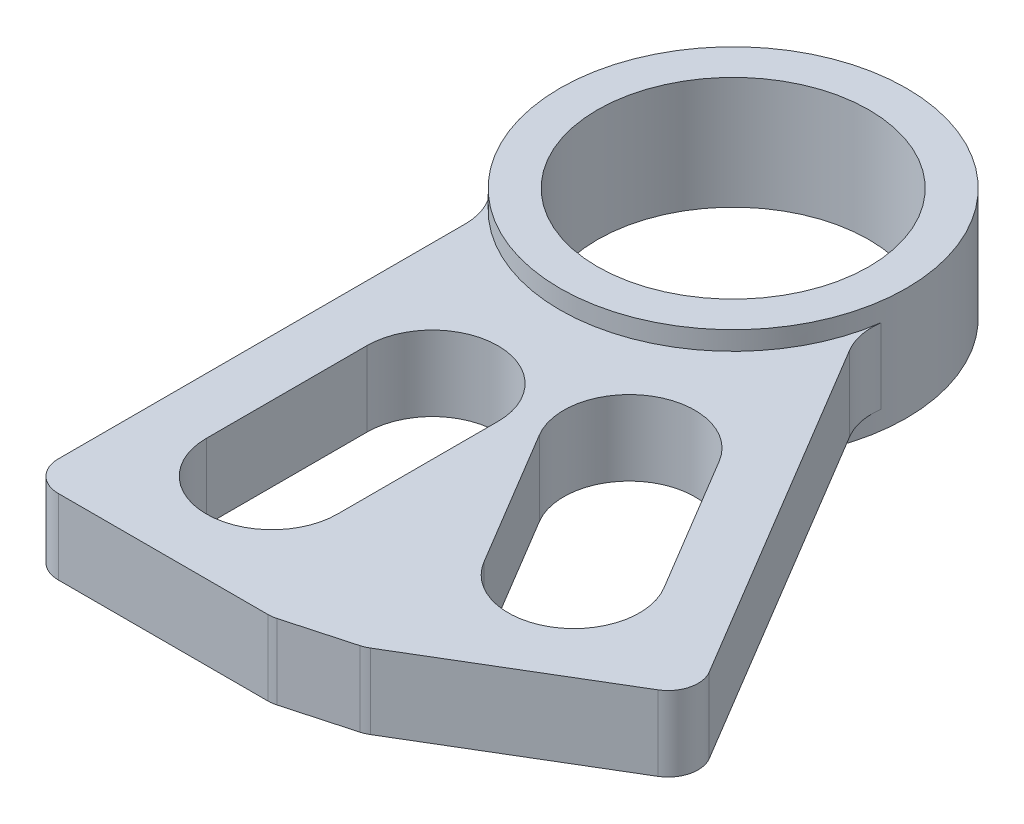
SolidWorks part; units mm, degrees
material "AISI 4130 Steel, normalized at 870C"
ref_plane "Front Plane" through (0, 0, 0) normal (0, 0, 1) x (1, 0, 0)
ref_plane "Top Plane" through (0, 0, 0) normal (0, 1, 0) x (1, 0, 0)
ref_plane "Right Plane" through (0, 0, 0) normal (1, 0, 0) x (0, 0, -1)
sketch "Sketch1" plane through (0, 0, 0) normal (0, 1, 0) x (1, 0, 0)
  line L0 (0, 0) -> (0, -49.3903) construction
  line L1 (0, 0) -> (25.3392, -42.3949) construction
  line L2 (0, -39.0716) -> (0, -25.4826) construction
  line L3 (-5.5562, -39.0716) -> (-5.5562, -25.4826)
  line L4 (5.5563, -39.0716) -> (5.5563, -25.4826)
  line L5 (20.0452, -33.5377) -> (13.0736, -21.8733) construction
  line L6 (15.276, -36.3882) -> (8.3043, -24.7239)
  line L7 (24.8145, -30.6871) -> (17.8428, -19.0228)
  line L8 (0, -49.3903) -> (0, -44.6278) construction
  line L9 (25.3392, -42.3949) -> (22.8958, -38.3069) construction
  line L10 (-10.3187, -49.3903) -> (10.3188, -49.3903)
  line L11 (16.4819, -47.6888) -> (34.1964, -37.101)
  line L12 (-10.3187, -49.3903) -> (-10.3187, -10.4432)
  line L13 (10.3188, -49.3903) -> (10.3188, -37.3773)
  line L14 (34.1964, -37.101) -> (14.215, -3.6702)
  line L15 (16.4819, -47.6888) -> (10.3188, -37.3773)
  line L16 (185.4194, -310.2248) -> (14.7508, -24.6795) construction
  line L17 (10.3188, -49.3903) -> (16.4819, -47.6888)
  line L22 (0, 0) -> (10.3188, -37.3773) construction
  circle A0 centre (0, 0) radius 11.5062
  circle A1 centre (0, 0) radius 14.6812
  arc A2 (-5.5562, -39.0716) -> (5.5563, -39.0716) centre (0, -39.0716) ccw
  arc A3 (5.5563, -25.4826) -> (-5.5562, -25.4826) centre (0, -25.4826) ccw
  arc A4 (15.276, -36.3882) -> (24.8145, -30.6871) centre (20.0452, -33.5377) ccw
  arc A5 (17.8428, -19.0228) -> (8.3043, -24.7239) centre (13.0736, -21.8733) ccw
  point P8 (0, -32.2771)
  point P13 (16.5594, -27.7055)
  point P25 (0, -49.3903)
  point P27 (25.3392, -42.3949)
  dimension "D2" = 29.3624
  dimension "D3" = 4.7625
  dimension "D4" = 4.7625
  dimension "D5" = 13.589
  dimension "D6" = 49.3903
  dimension "D7" = 20.6375
extrude "Bearing_Insert_Extrude" add sketch "Sketch1" along normal mid plane 9.525 contours A1 A0 region at (-5.4988, 0, -13.1636)
extrude "Apex_Slot_Insert_Extrude" add sketch "Sketch1<4>" along normal mid plane 6.35 contours A1 L12 L10 L13 L15 L11 L14 A5 L7 A4 L6 A3 L4 A2 L3 | L13 L17 L15 region at (8.3301, 0, 30.1737) region at (12.3731, 0, 44.8188)
sketch "Sketch1<4>" plane through (0, 0, 0) normal (0, 1, 0) x (1, 0, 0) same geometry as "Sketch1"
fillet "Fillet1" radius 5.08 2 edges at (14.215, 0, 3.6702) (-10.3187, 0, 10.4432)
fillet "Fillet2" radius 2.54 4 edges at (34.1964, 0, 37.101) (-10.3187, 0, 49.3903) (16.4819, 0, 47.6888) (10.3188, 0, 49.3903)
equation "\"Apex_thickness\"= .25"
equation "\"Bearing_diameter\"= 0.906in"
equation "\"A-arm_angle\"= 39.1893"
equation "\"D1@Sketch1\"=\"Bearing_diameter\""
equation "\"D1@Apex_Slot_Insert_Extrude\"=\"Apex_thickness\""
